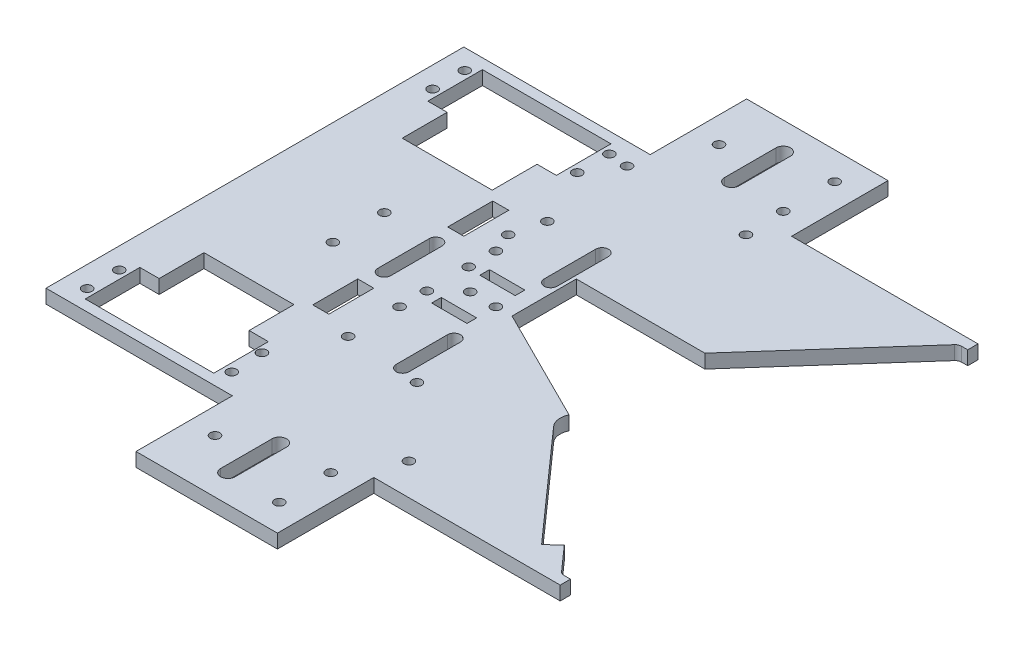
SolidWorks part; units mm, degrees
ref_plane "Front Plane" through (0, 0, 0) normal (0, 0, 1) x (1, 0, 0)
ref_plane "Top Plane" through (0, 0, 0) normal (0, 1, 0) x (1, 0, 0)
ref_plane "Right Plane" through (0, 0, 0) normal (1, 0, 0) x (0, 0, -1)
sketch "Sketch2" plane through (0, 0, 0) normal (0, 1, 0) x (1, 0, 0)
  line L2 (0, 0) -> (0, 65)
  line L3 (0, 65) -> (58, 65)
  line L4 (160, 0) -> (160, 65)
  line L8 (0, 0) -> (160, 0)
  line L9 (102, 65) -> (160, 65)
  line L11 (102, 65) -> (102, 95)
  line L12 (58, 65) -> (58, 95)
  line L13 (58, 95) -> (102, 95)
  dimension "D1" = 65
  dimension "D2" = 160
  dimension "D3" = 44
  dimension "D4" = 30
extrude "Boss-Extrude1" add sketch "Sketch2" along normal blind 4.3
mirror "Mirror1" about plane through (0, 4.3, 0) normal (0, 0, -1) of bodies 101
sketch "Sketch3" plane through (0, 4.3, 0) normal (0, 1, 0) x (1, 0, 0)
  line L0 (160, 61.8) -> (160, -61.8)
  line L1 (120.0126, 20) -> (157.1565, 61.8)
  line L3 (80.0126, 0) -> (80.0126, 20)
  line L4 (80.0126, 20) -> (120.0126, 20)
  line L12 (160, 65) -> (102, 65)
  line L13 (102, 65) -> (102, 95)
  line L15 (102, 95) -> (58, 95)
  line L16 (58, 65) -> (0, 65)
  line L17 (0, 65) -> (0, -65)
  line L18 (0, -65) -> (58, -65)
  line L20 (58, 95) -> (58, 65)
  line L22 (102, -65) -> (160, -65)
  line L23 (160, -65) -> (160, 65)
  line L36 (58, -65) -> (58, -95)
  line L38 (58, -95) -> (102, -95)
  line L39 (58, -95) -> (102, -95)
  line L40 (102, -95) -> (102, -65)
  line L42 (160, -61.8) -> (157.1556, -61.8)
  line L45 (160, 61.8) -> (157.1565, 61.8)
  line L48 (80.0126, 0) -> (120, -20)
  line L49 (120, -20) -> (157.1556, -61.8)
  line M24 (160, -65) -> (160, 65)
  dimension "D2" = 130
  dimension "D3" = 20
  dimension "D4" = 40
  dimension "D1" = 0
extrude "Cut-Extrude1" cut sketch "Sketch3" against normal blind 4.5 contours L48 L49 L1 L4 L3 M24 region at (132.7054, 4.3, -1.1594)
fillet "Fillet1" radius 2 2 edges at (157.1565, 2.15, -61.8) (157.1556, 2.15, 61.8)
ref_axis "Axis1" through (80, 4.3, 95) along (0, 0, -1)
sketch "Sketch4" plane through (0, 4.3, 0) normal (0, 1, 0) x (1, 0, 0)
  line L0 (80, -95) -> (80, 95)
  line L1 (102, -95) -> (58, -95) construction
  line L2 (102, 95) -> (58, 95) construction
ref_plane "Plane2" through (0, 4.3, 0) normal (0, 1, 0) x (1, 0, 0)
sketch "Sketch6" plane through (0, 4.3, 0) normal (0, 1, 0) x (1, 0, 0)
  line L3 (9, -61.8) -> (49, -61.8)
  line L6 (29, -45.8) -> (29, -44.8)
  line L7 (9, -44.8) -> (15, -44.8)
  line L11 (43, -44.8) -> (43, -30.8418)
  line L12 (15, -44.8) -> (15, -30.8418)
  line L13 (15, -30.8418) -> (43, -30.8418)
  line L15 (0, 0) -> (80.0126, 0)
  line L16 (80.0126, 0) -> (120, -20) construction
  line L18 (9, 44.8) -> (15, 44.8)
  line L20 (15, 30.8418) -> (43, 30.8418)
  line L21 (15, 44.8) -> (15, 30.8418)
  line L22 (43, 44.8) -> (43, 30.8418)
  line L25 (15, -45.8) -> (15, -30.8418) construction
  line L27 (9, 61.8) -> (49, 61.8)
  line L30 (4, -61.8) -> (3, -61.8)
  line L31 (0, -61.8) -> (160, -61.8) construction
  line L32 (3, -61.8) -> (4, -61.8)
  line L33 (3, -44.8) -> (3, -62.8) construction
  line L34 (3, -62.8) -> (55, -62.8) construction
  line L35 (55, -44.8) -> (55, -62.8) construction
  line L36 (4, -61.8) -> (54, -61.8) construction
  line L37 (0, 61.8) -> (160, 61.8) construction
  line L38 (54, 61.8) -> (55, 61.8)
  line L39 (54, 61.8) -> (55, 61.8)
  line L40 (43, 44.8) -> (49, 44.8)
  line L41 (4, -45.8) -> (4, -61.8) construction
  line L42 (4, -45.8) -> (54, -45.8) construction
  line L43 (43, -44.8) -> (49, -44.8)
  line L44 (3, -44.8) -> (55, -44.8) construction
  line L45 (29, -45.8) -> (29, -30.8418) construction
  line L46 (43, -45.8) -> (43, -30.8418) construction
  line L47 (54, -45.8) -> (54, -61.8) construction
  line L48 (9, -61.8) -> (49, -61.8)
  line L52 (9, 61.8) -> (9, 44.8)
  line L53 (55, 61.8) -> (54, 61.8)
  line L56 (49, 61.8) -> (49, 44.8)
  line L59 (3, -61.8) -> (4, -61.8)
  line L60 (9, -44.8) -> (9, -61.8)
  line L64 (49, -44.8) -> (49, -61.8)
  dimension "D4" = 1
  dimension "D5" = 14
  dimension "D6" = 14
extrude "Cut-Extrude2" cut sketch "Sketch6" against normal blind 10
sketch "Sketch8" plane through (0, 4.3, 0) normal (0, 1, 0) x (1, 0, 0)
  circle A0 centre (6.5, 58.8) radius 1.5
  circle A1 centre (6.5, 48.8) radius 1.5
  circle A2 centre (51.5, 48.8) radius 1.5
  circle A3 centre (51.5, 58.8) radius 1.5
  circle A4 centre (6.5, -48.7) radius 1.5
  circle A5 centre (6.5, -58.7) radius 1.5
  circle A6 centre (51.5, -58.7) radius 1.5
  circle A7 centre (51, -48.8) radius 1.5
  dimension "D7" = 3
extrude "Cut-Extrude3" cut sketch "Sketch8" against normal blind 10
sketch "Sketch9" plane through (0, 0, 0) normal (0, -1, 0) x (1, 0, 0)
  line L0 (75.75, 70.4) -> (75.75, 86.4)
  line L1 (75.75, -86.4) -> (75.75, -70.4)
  line L2 (80.25, -86.4) -> (80.25, -70.4)
  line L4 (80.25, 70.4) -> (80.25, 86.4)
  circle A0 centre (94, 70.4) radius 1.5
  circle A1 centre (66, 78.4) radius 1.5
  circle A2 centre (66, -78.4) radius 1.5
  circle A3 centre (94, -86.4) radius 1.5
  circle A4 centre (94, 86.4) radius 1.5
  circle A5 centre (94, -70.4) radius 1.5
  arc A6 (75.75, -86.4) -> (80.25, -86.4) centre (78, -86.4) ccw
  arc A7 (80.25, -70.4) -> (75.75, -70.4) centre (78, -70.4) ccw
  arc A10 (75.75, 70.4) -> (80.25, 70.4) centre (78, 70.4) ccw
  arc A12 (80.25, 86.4) -> (75.75, 86.4) centre (78, 86.4) ccw
  dimension "D1" = 3
extrude "Cut-Extrude4" cut sketch "Sketch9" against normal blind 10
sketch "Sketch7" plane through (0, 4.3, 0) normal (0, 1, 0) x (1, 0, 0)
  line L0 (0, 0) -> (80.0126, 0)
  line L1 (0, 65) -> (0, -65) construction
  line L2 (80.0126, 0) -> (80.0126, 20) construction
  line L3 (80, -95) -> (80, 95) construction
  line L4 (64, -9) -> (75, -9)
  line L5 (64, -6) -> (75, -6)
  line L6 (64, -9) -> (64, -6)
  line L7 (75, -9) -> (75, -6)
  line L8 (64, -7.5) -> (75, -7.5)
  line L9 (64, 7.5) -> (75, 7.5)
  line L10 (75, 9) -> (75, 6)
  line L11 (64, 9) -> (64, 6)
  line L12 (64, 6) -> (75, 6)
  line L13 (64, 9) -> (75, 9)
  circle A0 centre (60.0126, -6.5) radius 1.5
  circle A1 centre (60.0126, 6.5) radius 1.5
  dimension "D1" = 3
  dimension "D2" = 6.5
  dimension "D3" = 20
  dimension "D6" = 11
  dimension "D4" = 5
  dimension "D5" = 3
  dimension "D7" = 7.5
sketch "Sketch10" plane through (0, 4.3, 0) normal (0, 1, 0) x (1, 0, 0)
  line L0 (120, -20) -> (156.5589, -61.1287) construction
  line L1 (123.3218, -23.737) -> (149.8964, -53.6334)
  line L2 (116.263, -23.3218) -> (146.1593, -56.9552)
  line L3 (149.8964, -53.6334) -> (146.1593, -56.9552)
  line L4 (120, -20) -> (156.5589, -61.1287) construction
  line L5 (116.263, -23.3218) -> (152.8218, -64.4505) construction
  arc A0 (123.3218, -23.737) -> (116.263, -23.3218) centre (120, -20) ccw
  dimension "D1" = 5
  dimension "D2" = 45
extrude "Cut-Extrude5" cut sketch "Sketch10" against normal blind 10
sketch "Sketch11" plane through (0, 0, 0) normal (0, -1, 0) x (1, 0, 0)
  line L0 (0, 0) -> (80.0126, 0) construction
  line L1 (80, 95) -> (80, -95) construction
  line L2 (80.0126, 0) -> (0, 0)
  line L4 (75, 31.0313) -> (75, 15.0313)
  line L6 (79, 31.0313) -> (79, 15.0313)
  line L7 (79, -31.0313) -> (79, -15.0313)
  line L8 (75, -31.0313) -> (75, -15.0313)
  circle A0 centre (60, 31) radius 1.5
  circle A1 centre (60, 15) radius 1.5
  arc A2 (75, 31.0313) -> (79, 31.0313) centre (77, 31.0313) cw
  arc A3 (75, 15.0313) -> (79, 15.0313) centre (77, 15.0313) ccw
  arc A4 (75, -15.0313) -> (79, -15.0313) centre (77, -15.0313) cw
  arc A5 (75, -31.0313) -> (79, -31.0313) centre (77, -31.0313) ccw
  circle A6 centre (60, -15) radius 1.5
  circle A7 centre (60, -31) radius 1.5
  dimension "D1" = 3
  dimension "D2" = 16
  dimension "D3" = 15
  dimension "D4" = 20
  dimension "D5" = 15
  dimension "D6" = 4
extrude "Cut-Extrude6" cut sketch "Sketch11" against normal blind 10 contours L4 A3 L6 A2 | L8 A5 L7 A4 | A7 | A0 | A1 | A6 region at (77, 0, 23.0313) region at (77, 0, -23.0313) region at (60, 0, -31)
sketch "Sketch12" plane through (0, 0, 0) normal (0, -1, 0) x (-1, 0, 0)
  line L0 (0, 0) -> (-80.0126, 0) construction
  line L3 (-50.2627, -8) -> (-50.2627, 8)
  line L4 (-50.2627, 0) -> (-46.2627, 0)
  line L5 (-46.2627, -8) -> (-46.2627, 8)
  line L6 (0, 0) -> (-46.2627, 0)
  line L7 (0, 65) -> (0, -65) construction
  line L8 (-160, -61.8) -> (0, -61.8) construction
  line L9 (-80.0126, 0) -> (-50.2627, 0)
  line L10 (-80.0126, 0) -> (-115.5281, -17.7634) construction
  line L11 (-80.0126, 0) -> (-80.0126, 20) construction
  line L12 (-58, -65) -> (0, -65) construction
  line L13 (-58, 65) -> (0, 65) construction
  circle A0 centre (-32.2627, -8) radius 1.5
  circle A1 centre (-32.2627, 8) radius 1.5
  arc A2 (-46.2627, 8) -> (-50.2627, 8) centre (-48.2627, 8) ccw
  arc A3 (-50.2627, -8) -> (-46.2627, -8) centre (-48.2627, -8) ccw
  circle A5 centre (-32.2627, -8) radius 1.5 construction
  circle A6 centre (-32.2627, 8) radius 1.5 construction
  dimension "D1" = 3
  dimension "D8" = 8
  dimension "D9" = 8
  dimension "D2" = 8
  dimension "D3" = 14
  dimension "D4" = 4
  dimension "D5" = 61.8
  dimension "D6" = 65
  dimension "D7" = 65
extrude "Cut-Extrude7" cut sketch "Sketch12" against normal blind 10 contours A3 L5 L4 L3 | L4 L5 A2 L3 | A0 | A1 region at (48.2627, 0, 4.7958) region at (48.2627, 0, -4.7958) region at (32.2627, 0, 8) region at (32.2627, 0, -8)
extrude "Cut-Extrude8" cut sketch "Sketch7" against normal blind 9 contours A0 | L4 L7 L5 L6 | L12 L10 L13 L11 | A1
sketch "Sketch13" plane through (0, 4.3, 0) normal (0, 1, 0) x (1, 0, 0)
  line L0 (80.0126, 0) -> (59.0194, 0)
  line L1 (80, -95) -> (80, 95) construction
  circle A0 centre (67, 0) radius 1.5
  circle A1 centre (75, 0) radius 1.5
  dimension "D2" = 3
  dimension "D3" = 5
  dimension "D1" = 8
extrude "Cut-Extrude9" cut sketch "Sketch13" against normal blind 10 contours L0 A0 | L0 A0 | L0 A1 | L0 A1 region at (75, 4.3, 0.6366) region at (75, 4.3, -0.6366) region at (67, 4.3, 0.6366) region at (67, 4.3, -0.6366)
sketch "Sketch14" plane through (0, 4.3, 0) normal (0, 1, 0) x (1, 0, 0)
  circle A0 centre (57.5, 58.3) radius 1.5
  circle A1 centre (94.5, 58.3) radius 1.5
  circle A2 centre (57.5, 21.3) radius 1.5
  circle A3 centre (83.1278, -32.706) radius 1.5
  circle A4 centre (103.0587, -55.1282) radius 1.5
  dimension "D1" = 3
  dimension "D2" = 3
extrude "Cut-Extrude10" cut sketch "Sketch14" against normal blind 10
sketch "Sketch15" plane through (0, 4.3, 0) normal (0, 1, 0) x (1, 0, 0)
  line L1 (46, 28) -> (51, 28)
  line L2 (46, 28) -> (46, 14)
  line L3 (46, 14) -> (51, 14)
  line L4 (51, 28) -> (51, 14)
  line L6 (0, 65) -> (0, -65) construction
  line L7 (80.0126, 0) -> (53.7017, 0)
  line L8 (46, -14) -> (51, -14)
  line L9 (51, -28) -> (51, -14)
  line L10 (46, -28) -> (51, -28)
  line L11 (46, -28) -> (46, -14)
  arc A0 (50.2627, 8) -> (46.2627, 8) centre (48.2627, 8) ccw construction
  arc A1 (46.2627, -8) -> (50.2627, -8) centre (48.2627, -8) ccw construction
  dimension "D1" = 46
  dimension "D2" = 5
  dimension "D3" = 14
  dimension "D4" = 14
  dimension "D5" = 14
  dimension "D6" = 6
  dimension "D7" = 6
extrude "Cut-Extrude11" cut sketch "Sketch15" against normal blind 10 contours L4 L1 L2 L3 | L11 L10 L9 L8 region at (48.5, 4.3, -21) region at (48.5, 4.3, 21)
